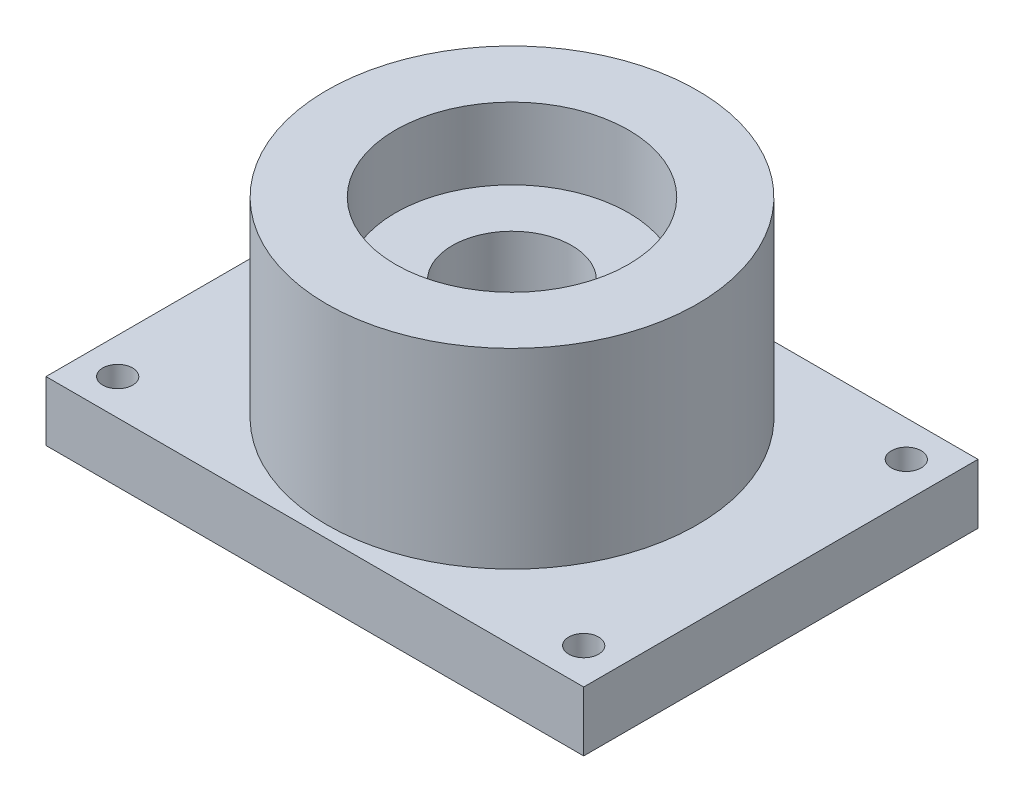
SolidWorks part; units mm, degrees
ref_plane "Front Plane" through (0, 0, 0) normal (0, 0, 1) x (1, 0, 0)
ref_plane "Top Plane" through (0, 0, 0) normal (0, 1, 0) x (1, 0, 0)
ref_plane "Right Plane" through (0, 0, 0) normal (1, 0, 0) x (0, 0, -1)
sketch "Sketch1" plane through (0, 0, 0) normal (0, 1, 0) x (1, 0, 0)
  circle A0 centre (0, 0) radius 15.5
  dimension "D1" = 31
extrude "Boss-Extrude1" add sketch "Sketch1" along normal blind 16
ref_plane "Plane1" through (0, 0, 0) normal (0, -1, 0) x (-1, 0, 0)
sketch "Sketch16" plane through (0, 0, 0) normal (0, -1, 0) x (1, 0, 0)
  line L0 (0, 0) -> (22.5, 16.5) construction
  line L1 (-22.5, 16.5) -> (22.5, 16.5)
  line L2 (-22.5, 16.5) -> (-22.5, -16.5)
  line L3 (-22.5, -16.5) -> (22.5, -16.5)
  line L4 (22.5, 16.5) -> (22.5, -16.5)
  line L5 (-22.5, 16.5) -> (22.5, -16.5) construction
  circle A0 centre (-19.5, -13.5) radius 1.25
  circle A1 centre (19.5, -13.5) radius 1.25
  circle A2 centre (19.5, 13.5) radius 1.25
  circle A3 centre (-19.5, 13.5) radius 1.25
  point P0 (0, 0)
  dimension "D3" = 2.5
  dimension "D5" = 3
  dimension "D1" = 33
  dimension "D2" = 45
  dimension "D4" = 3
  dimension "D6" = 2
  dimension "D7" = 2
extrude "Boss-Extrude6" add sketch "Sketch16" along normal blind 5
sketch "Sketch17" plane through (0, 16, 0) normal (0, 1, 0) x (1, 0, 0)
  circle A0 centre (0, 0) radius 9.75
  dimension "D1" = 19.5
extrude "Cut-Extrude5" cut sketch "Sketch17" against normal blind 6
sketch "Sketch18" plane through (0, 10, 0) normal (0, 1, 0) x (1, 0, 0)
  circle A0 centre (0, 0) radius 5
  dimension "D1" = 10
extrude "Cut-Extrude7" cut sketch "Sketch18" against normal blind 19
